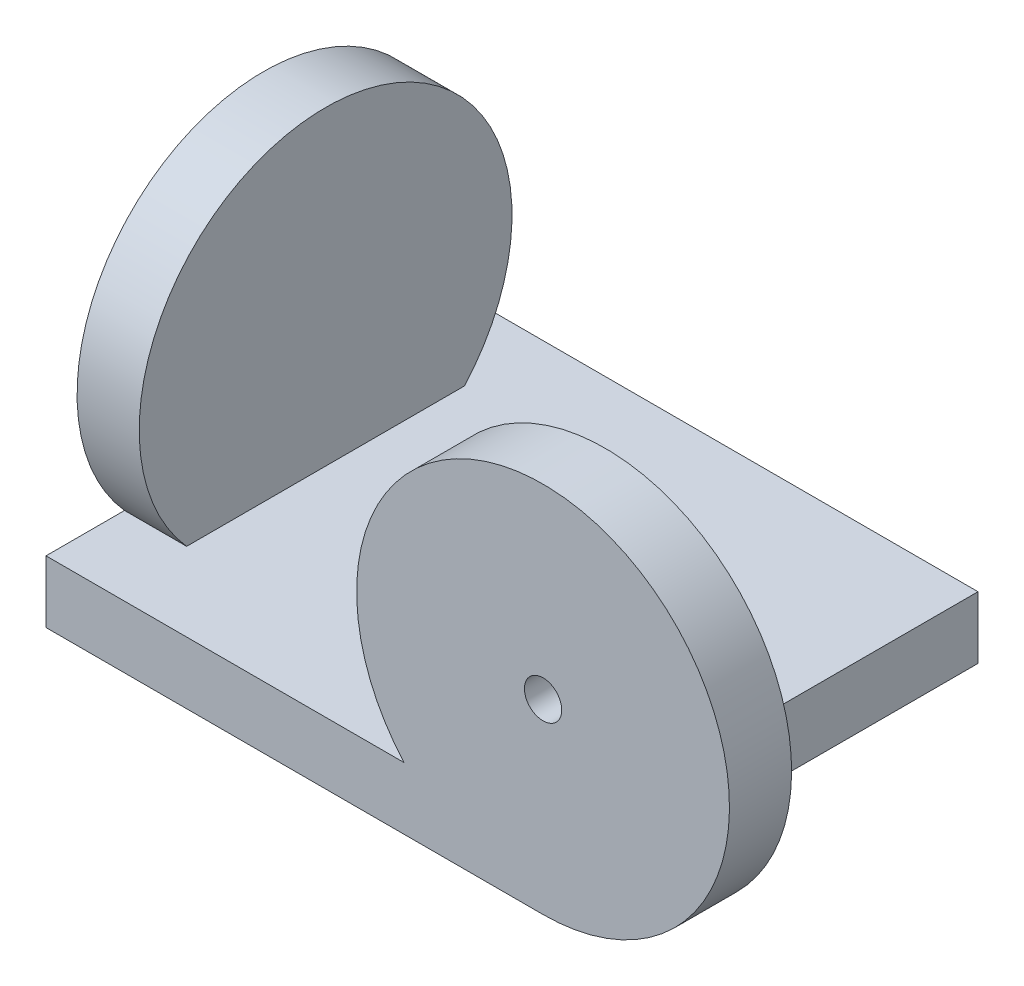
SolidWorks part; units mm, degrees
ref_plane "Front Plane" through (0, 0, 0) normal (0, 0, 1) x (1, 0, 0)
ref_plane "Top Plane" through (0, 0, 0) normal (0, 1, 0) x (1, 0, 0)
ref_plane "Right Plane" through (0, 0, 0) normal (1, 0, 0) x (0, 0, -1)
sketch "Sketch1" plane through (0, 0, 0) normal (0, 0, 1) x (1, 0, 0)
  circle A0 centre (0, 0) radius 30
  dimension "D1" = 60
extrude "Boss-Extrude1" add sketch "Sketch1" along normal blind 10 contours A0
sketch "Sketch2" plane through (0, 0, 10) normal (0, 0, 1) x (1, 0, 0)
  line L1 (0, -30) -> (-80, -30)
  line L2 (0, -30) -> (0, -20)
  line L3 (0, -20) -> (-80, -20)
  line L4 (-80, -30) -> (-80, -20)
  circle A0 centre (0, 0) radius 30 construction
  dimension "D1" = 10
  dimension "D2" = 80
extrude "Boss-Extrude2" add sketch "Sketch2" against normal blind 70
sketch "Sketch3" plane through (-80, 0, 0) normal (-1, 0, 0) x (0, 0, 1)
  line L1 (-60, -20) -> (10, -20) construction
  line L2 (-60, -30) -> (10, -30) construction
  circle A1 centre (-25, 0) radius 30
  point P5 (-25, -20)
  dimension "D1" = 60
extrude "Boss-Extrude3" add sketch "Sketch3" against normal blind 10 contours A1
hole_wizard "Ø6.0mm Dowel Hole2" positions "Sketch6" profile "Sketch7" hole size "Ø6.0" standard "ANSI Metric" end condition through all
sketch "Sketch6" plane through (0, 0, 0) normal (0, 0, -1) x (-1, 0, 0)
  point P0 (0, 0)
sketch "Sketch7" plane through (0, 0, 0) normal (1, 0, 0) x (0, 1, 0)
  line L0 (0, 0) -> (0, 10)
  line L1 (0, 10) -> (3, 10)
  line L2 (3, 10) -> (3, 0)
  line L5 (3, 0) -> (0, 0)
  line L11 (0, -6.35) -> (0, 107.95) construction
  dimension "Thru Hole Dia." = 6
  dimension "Thru Hole Depth" = 10
hole_wizard "M4x0.7 Tapped Hole1" positions "Sketch8" profile "Sketch9" tap size "M4x0.7" standard "ANSI Metric"
sketch "Sketch8" plane through (0, 0, 0) normal (0, 0, -1) x (-1, 0, 0)
  point P0 (-15.5, 15.5)
  point P2 (15.5, 15.5)
  point P4 (15.5, -15.5)
  point P6 (-15.5, -15.5)
  point P11 (-14.6864, -12.2228)
  point P12 (0, 0)
  point P13 (0, 0)
  point P14 (0, 0)
  point P15 (0, 0)
  point P17 (0, 0)
  dimension "D1" = 31
  dimension "D2" = 31
  dimension "D3" = 15.5
  dimension "D4" = 15.5
sketch "Sketch9" plane through (15.5, 15.5, 0) normal (1, 0, 0) x (0, 1, 0)
  line L0 (0, 0) -> (0, 6.9914)
  line L1 (0, 6.9914) -> (1.65, 6)
  line L2 (1.65, 6) -> (1.65, 0)
  line L5 (1.65, 0) -> (0, 0)
  line L10 (0, 6.9914) -> (-1.65, 6) construction
  line L11 (0, -6.35) -> (0, 107.95) construction
  dimension "Tap Drill Dia." = 3.3
  dimension "Tap Drill Depth" = 6
  dimension "Drill Angle" = 118
cosmetic thread "Hole Thread1" parameters "D1"=5, "D2"=4
cosmetic thread "Hole Thread2" parameters "D1"=5, "D2"=4
cosmetic thread "Hole Thread3" parameters "D1"=5, "D2"=4
cosmetic thread "Hole Thread4" parameters "D1"=5, "D2"=4
